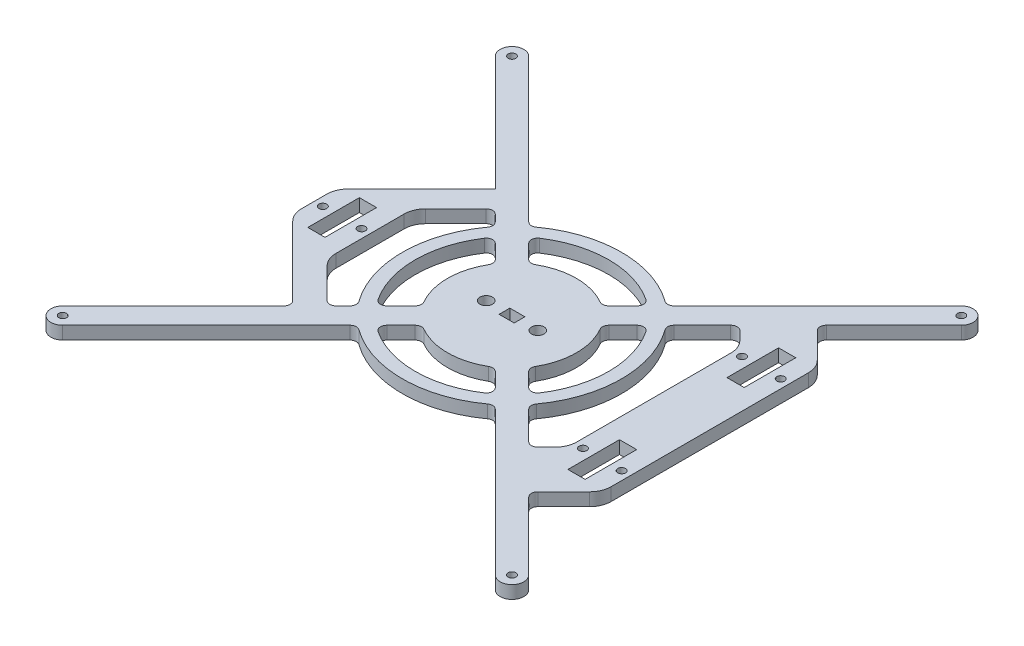
SolidWorks part; units mm, degrees
material "3003-O"
ref_plane "Front Plane" through (0, 0, 0) normal (0, 0, 1) x (1, 0, 0)
ref_plane "Top Plane" through (0, 0, 0) normal (0, 1, 0) x (1, 0, 0)
ref_plane "Right Plane" through (0, 0, 0) normal (1, 0, 0) x (0, 0, -1)
sketch "Sketch1" plane through (0, 0, 0) normal (0, 1, 0) x (1, 0, 0)
  line L0 (-110, -110) -> (110, 110) construction
  line L1 (-110, 110) -> (110, 110)
  line L2 (-110, 110) -> (-110, -110)
  line L3 (-110, -110) -> (110, -110)
  line L4 (110, 110) -> (110, -110)
  line L5 (-79, 110) -> (-79, -110) construction
  line L6 (75, 25) -> (75, -25) construction
  line L7 (0, 110) -> (0, -110) construction
  line L8 (-75, 0) -> (-70, 0) construction
  line L9 (0, 0) -> (70, 0) construction
  line L10 (-70, 0) -> (0, 0) construction
  line L11 (-83, 12) -> (-75, 12)
  line L12 (-83, 12) -> (-83, -12)
  line L13 (-83, -12) -> (-75, -12)
  line L14 (-75, 12) -> (-75, -12)
  line L15 (70, 0) -> (75, 0) construction
  line L16 (-83, 0) -> (-88, 0) construction
  line L17 (83, 37) -> (88, 37) construction
  line L18 (75, 49) -> (83, 49)
  line L19 (75, 49) -> (75, 25)
  line L20 (75, 25) -> (83, 25)
  line L21 (83, 49) -> (83, 25)
  line L22 (75, -25) -> (83, -25)
  line L23 (75, -25) -> (75, -49)
  line L24 (75, -49) -> (83, -49)
  line L25 (83, -25) -> (83, -49)
  line L26 (75, 37) -> (70, 37) construction
  line L27 (75, -37) -> (70, -37) construction
  line L28 (83, -37) -> (88, -37) construction
  circle A0 centre (-104.5, 104.5) radius 1.8
  circle A1 centre (104.5, 104.5) radius 1.8
  circle A2 centre (104.5, -104.5) radius 1.8
  circle A3 centre (-104.5, -104.5) radius 1.8
  circle A4 centre (-70, 0) radius 1.8
  circle A5 centre (-88, 0) radius 1.8
  circle A6 centre (88, 37) radius 1.8
  circle A7 centre (70, 37) radius 1.8
  circle A8 centre (88, -37) radius 1.8
  circle A9 centre (70, -37) radius 1.8
  point P26 (-79, 12)
  dimension "D3" = 3.6
  dimension "D4" = 5.5
  dimension "D5" = 5.5
  dimension "D9" = 150
  dimension "D10" = 209
  dimension "D1" = 220
  dimension "D2" = 50
  dimension "D6" = 24
  dimension "D7" = 8
  dimension "D8" = 5
extrude "Boss-Extrude1" add sketch "Sketch1" along normal mid plane 6
sketch "Sketch2" plane through (0, -3, 0) normal (0, -1, 0) x (1, 0, 0)
  line L0 (-104.5, 104.5) -> (104.5, -104.5) construction
  line L1 (-110, 110) -> (110, 110)
  line L2 (-110, 110) -> (-110, -110)
  line L3 (-110, -110) -> (110, -110)
  line L4 (110, 110) -> (110, -110)
  line L5 (104.5, 104.5) -> (-104.5, -104.5) construction
  line L6 (-100.6109, 108.3891) -> (-108.3891, 100.6109)
  line L7 (-108.3891, 100.6109) -> (-24.7427, 16.9646)
  line L8 (-100.6109, 108.3891) -> (-16.9646, 24.7427)
  line L9 (-24.7427, 16.9646) -> (-16.9646, 24.7427)
  line L10 (-108.3891, -100.6109) -> (-100.6109, -108.3891)
  line L11 (-100.6109, -108.3891) -> (-16.9646, -24.7427)
  line L12 (-16.9646, -24.7427) -> (-24.7427, -16.9646)
  line L13 (-24.7427, -16.9646) -> (-108.3891, -100.6109)
  line L14 (-92, 5.8579) -> (-92, -5.8579)
  line L15 (-66, 15.8579) -> (-66, -15.8579)
  line L16 (100.6109, -108.3891) -> (108.3891, -100.6109)
  line L17 (108.3891, -100.6109) -> (24.7427, -16.9646)
  line L18 (24.7427, -16.9646) -> (16.9646, -24.7427)
  line L19 (16.9646, -24.7427) -> (100.6109, -108.3891)
  line L20 (100.6109, 108.3891) -> (108.3891, 100.6109)
  line L21 (108.3891, 100.6109) -> (24.7427, 16.9646)
  line L22 (24.7427, 16.9646) -> (16.9646, 24.7427)
  line L23 (16.9646, 24.7427) -> (100.6109, 108.3891)
  line L24 (0, 0) -> (-12, 0) construction
  line L25 (0, 0) -> (12, 0) construction
  line L26 (-70, 0) -> (-66, 0) construction
  line L27 (-88, 0) -> (-92, 0) construction
  line L28 (-89.0711, 12.9289) -> (-54.8891, 47.1109)
  line L29 (-63.0711, 22.9289) -> (-46.8891, 39.1109)
  line L30 (-89.0711, -12.9289) -> (-54.8891, -47.1109)
  line L31 (-63.0711, -22.9289) -> (-46.8891, -39.1109)
  line L32 (92, 45.8579) -> (92, -45.8579)
  line L33 (66, 35.8579) -> (66, -35.8579)
  line L34 (70, 37) -> (66, 37) construction
  line L35 (88, 37) -> (92, 37) construction
  line L36 (63.0711, -42.9289) -> (56.8891, -49.1109)
  line L37 (89.0711, -52.9289) -> (74.8891, -67.1109)
  line L38 (89.0711, 52.9289) -> (74.8891, 67.1109)
  line L39 (63.0711, 42.9289) -> (56.8891, 49.1109)
  line L40 (92, 0) -> (66, 0) construction
  line L41 (66, 0) -> (0, 0) construction
  circle A0 centre (-104.5, 104.5) radius 5.5
  arc A1 (89.0711, -52.9289) -> (92, -45.8579) centre (82, -45.8579) ccw
  arc A2 (63.0711, -42.9289) -> (66, -35.8579) centre (56, -35.8579) ccw
  circle A3 centre (-104.5, -104.5) radius 5.5
  circle A4 centre (0, 0) radius 30
  circle A5 centre (104.5, 104.5) radius 5.5
  circle A6 centre (104.5, -104.5) radius 5.5
  circle A7 centre (0, 0) radius 51
  circle A8 centre (0, 0) radius 45
  arc A9 (66, 35.8579) -> (63.0711, 42.9289) centre (56, 35.8579) ccw
  arc A10 (92, 45.8579) -> (89.0711, 52.9289) centre (82, 45.8579) ccw
  arc A11 (-63.0711, -22.9289) -> (-66, -15.8579) centre (-56, -15.8579) cw
  arc A12 (-66, 15.8579) -> (-63.0711, 22.9289) centre (-56, 15.8579) cw
  arc A13 (-89.0711, -12.9289) -> (-92, -5.8579) centre (-82, -5.8579) cw
  arc A14 (-92, 5.8579) -> (-89.0711, 12.9289) centre (-82, 5.8579) cw
  point P22 (-104.5, 104.5)
  point P27 (-104.5, -104.5)
  point P44 (104.5, -104.5)
  point P50 (104.5, 104.5)
  point P77 (92, -50)
  point P80 (66, -40)
  point P83 (66, 40)
  point P86 (92, 50)
  point P89 (-66, -20)
  point P92 (-66, 20)
  point P95 (-92, -10)
  point P98 (-92, 10)
  line M27 (-110, 110) -> (-110, -110)
  line M28 (-110, -110) -> (110, -110)
  line M29 (110, -110) -> (110, 110)
  line M30 (110, 110) -> (-110, 110)
  dimension "D1" = 11
  dimension "D3" = 4
  dimension "D4" = 11
  dimension "D6" = 60
  dimension "D7" = 6
  dimension "D8" = 90
  dimension "D10" = 20
  dimension "D11" = 4
  dimension "D15" = 10
  dimension "D16" = 10
  dimension "D2" = 11
  dimension "D5" = 11
  dimension "D9" = 12
  dimension "D12" = 40
  dimension "D13" = 100
  dimension "D14" = 80
extrude "Cut-Extrude1" cut sketch "Sketch2" against normal blind 10 contours A0 L1 M27 | L14 A14 L28 L7 A0 L2 A3 L13 L30 A13 | A7 L23 A5 L1 A0 L8 | A12 L15 A11 L31 L13 A7 L7 L29 | L7 A8 L13 A4 | L23 A8 L8 A4 | L17 A8 L21 A4 | L11 A8 L19 A4 | A7 L11 A3 L3 A6 L19 | A3 M27 M28 | A10 L32 A1 L37 L17 A6 L4 A5 L21 L38 | A6 M28 M29 | A5 L4 M30 | L33 A9 L39 L21 A7 L17 L36 A2 region at (-108.7715, -3, 108.7715) region at (0, -3, 83.025) region at (-109.781, -3, 102.3125) region at (108.7715, -3, 108.7715) region at (-108.7715, -3, -108.7715) region at (99.0573, -3, 0) region at (0, -3, -83.025) region at (108.7715, -3, -108.7715) region at (0, -3, 35.5609) region at (-54.8358, -3, 0) region at (56.0973, -3, 0) region at (-35.5609, -3, 0) region at (35.5609, -3, 0) region at (0, -3, -35.5609)
fillet "Fillet1" radius 3 31 edges at (-39.7412, 0, 31.963) (-31.963, 0, -39.7412) (-39.7412, 0, -31.963) (-24.7427, 0, -16.9646) (-24.7427, 0, 16.9646) (-35.4703, 0, 27.6922) (-35.4703, 0, -27.6922) (-27.6922, 0, -35.4703) (27.6922, 0, -35.4703) (-16.9646, 0, -24.7427) (16.9646, 0, -24.7427) (31.963, 0, -39.7412) (39.7412, 0, -31.963) (24.7427, 0, -16.9646) (35.4703, 0, -27.6922) (24.7427, 0, 16.9646) (16.9646, 0, 24.7427) (-16.9646, 0, 24.7427) (35.4703, 0, 27.6922) (39.7412, 0, 31.963) (27.6922, 0, 35.4703) (31.963, 0, 39.7412) (-27.6922, 0, 35.4703) (-31.963, 0, 39.7412) (74.8891, 0, -67.1109) (-46.8891, 0, -39.1109) (56.8891, 0, -49.1109) (56.8891, 0, 49.1109) (74.8891, 0, 67.1109) (-54.8891, 0, 47.1109) (-46.8891, 0, 39.1109)
hole_wizard "M5 Clearance Hole1" positions "3DSketch1" profile "Sketch3" hole size "M5" standard "ANSI Metric" end condition through all
sketch3d "3DSketch1"
  point P0 (-12, -3, 0)
  point P3 (12, -3, 0)
sketch "Sketch3" plane through (-12, -3, 0) normal (1, 0, 0) x (0, 0, -1)
  line L0 (0, 0) -> (0, 6)
  line L1 (0, 6) -> (2.9, 6)
  line L2 (2.9, 6) -> (2.9, 0)
  line L5 (2.9, 0) -> (0, 0)
  line L11 (0, -6.35) -> (0, 107.95) construction
  dimension "Thru Hole Dia." = 5.8
  dimension "Thru Hole Depth" = 6
sketch "Sketch4" plane through (0, 3, 0) normal (0, 1, 0) x (1, 0, 0)
  line L0 (-12, 0) -> (-3.5, 0) construction
  line L1 (-3.5, -2.5) -> (3.5, -2.5)
  line L2 (-3.5, -2.5) -> (-3.5, 2.5)
  line L3 (-3.5, 2.5) -> (3.5, 2.5)
  line L4 (3.5, -2.5) -> (3.5, 2.5)
  line L5 (12, 0) -> (3.5, 0) construction
  dimension "D1" = 5
  dimension "D2" = 7
extrude "Cut-Extrude2" cut sketch "Sketch4" against normal through all
